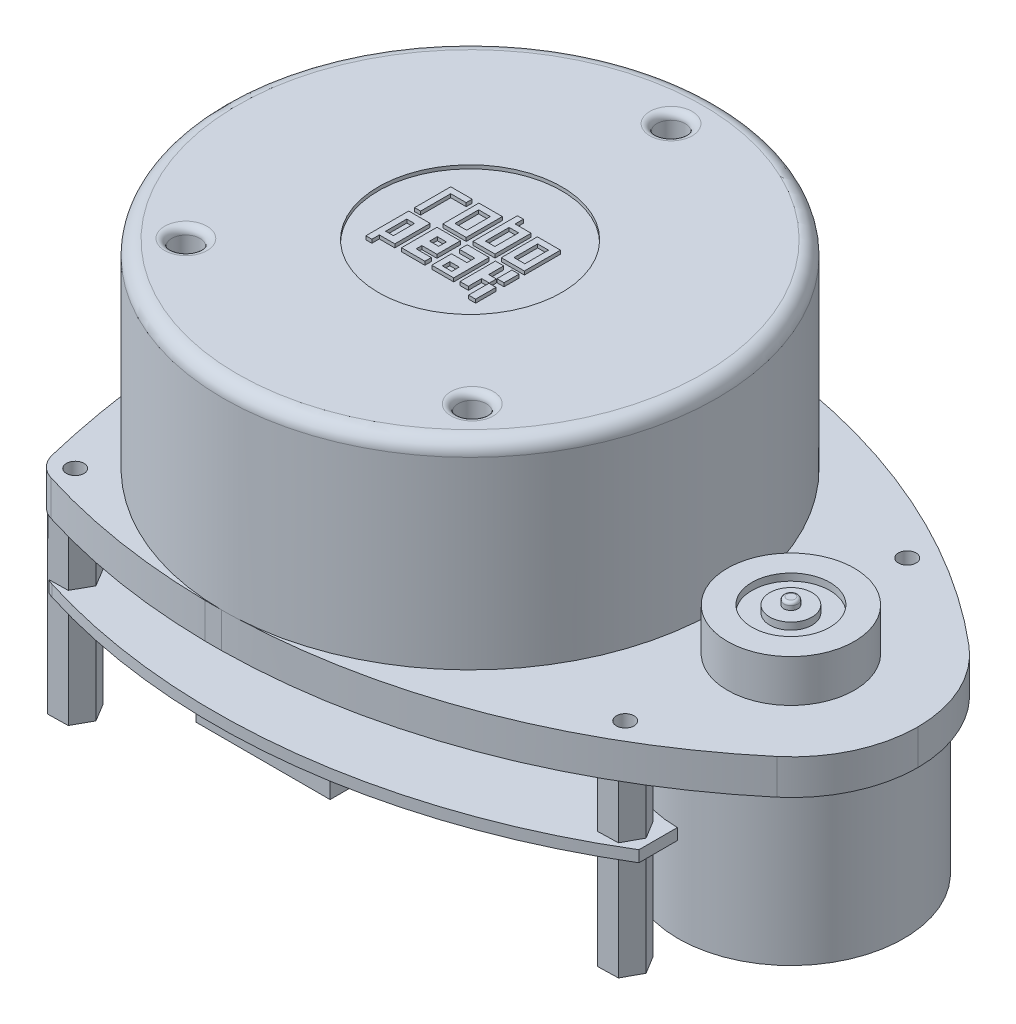
SolidWorks part; units mm, degrees
ref_plane "Спереди" through (0, 0, 0) normal (0, 0, 1) x (1, 0, 0)
ref_plane "Сверху" through (0, 0, 0) normal (0, 1, 0) x (1, 0, 0)
ref_plane "Справа" through (0, 0, 0) normal (1, 0, 0) x (0, 0, -1)
sketch "Эскиз1" plane through (0, 0, 0) normal (0, 1, 0) x (1, 0, 0)
  line L1 (-49.25, 35) -> (49.25, 35)
  line L2 (-49.25, 35) -> (-49.25, -35)
  line L3 (-49.25, -35) -> (49.25, -35)
  line L4 (49.25, 35) -> (49.25, -35)
  line L5 (-49.25, 35) -> (49.25, -35) construction
  line L6 (-49.25, -35) -> (49.25, 35) construction
  point P0 (0, 0)
  dimension "D1" = 98.5
  dimension "D2" = 70
extrude "Бобышка-Вытянуть1" add sketch "Эскиз1" along normal blind 5
sketch "Эскиз2" plane through (0, 5, 0) normal (0, 1, 0) x (1, 0, 0)
  line L0 (-49.25, 35) -> (-49.25, -35) construction
  circle A0 centre (-14.25, 0) radius 35
  point P2 (-49.25, 0)
  point P3 (-49.25, 0)
extrude "Бобышка-Вытянуть2" add sketch "Эскиз2" along normal blind 28.1
sketch "Эскиз3" plane through (0, 33.1, 0) normal (0, 1, 0) x (1, 0, 0)
  line L0 (-14.25, 0) -> (-14.25, 50000) construction
  line L1 (-14.25, -20) -> (-26.2883, -20) construction
  line L2 (-49.25, -35) -> (-14.25, -35) construction
  circle A0 centre (-14.25, 28.5) radius 2
  circle A1 centre (-34.5539, -20) radius 2
  circle A2 centre (6.0539, -20) radius 2
  arc A3 (-49.25, 0) -> (-14.25, -35) centre (-14.25, 0) ccw construction
  circle A4 centre (-14.25, 0) radius 35 construction
  dimension "D2" = 4
  dimension "D1" = 6.5
  dimension "D3" = 15
  dimension "D4" = 28.5
  dimension "D5" = 28.5
extrude "Вырез-Вытянуть1" cut sketch "Эскиз3" against normal blind 5
fillet "Скругление1" radius 2 1 edges at (-14.25, 33.1, 35)
fillet "Скругление2" radius 1 3 edges at (6.0539, 33.1, 22) (-34.5539, 33.1, 22) (-14.25, 33.1, -26.5)
sketch "Эскиз4" plane through (0, 33.1, 0) normal (0, 1, 0) x (1, 0, 0)
  line L0 (-22.1152, -6.9149) -> (-22.1152, -0.8316)
  line L1 (-22.1152, -0.8316) -> (-19.0735, -0.8316)
  line L2 (-19.0735, -0.8316) -> (-19.0735, -5.8538)
  line L3 (-19.0735, -5.8538) -> (-21.2663, -5.8538)
  line L4 (-21.2663, -5.8538) -> (-21.2663, -6.9149)
  line L5 (-21.2663, -6.9149) -> (-22.1152, -6.9149)
  line L6 (-22.1152, 0) -> (-22.1152, 5.1201)
  line L7 (-22.1152, 5.1201) -> (-19.0735, 5.1201)
  line L8 (-19.0735, 5.1201) -> (-19.0735, 4.2707)
  line L9 (-19.0735, 4.2707) -> (-21.2663, 4.2707)
  line L10 (-21.2663, 4.2707) -> (-21.2663, 0)
  line L11 (-21.2663, 0) -> (-22.1152, 0)
  line L12 (-21.2663, -1.9579) -> (-20.1699, -1.9579)
  line L13 (-20.1699, -1.9579) -> (-20.1699, -4.9509)
  line L14 (-20.1699, -4.9509) -> (-21.2663, -4.9509)
  line L15 (-21.2663, -4.9509) -> (-21.2663, -1.9579)
  line L16 (-13.8296, 0) -> (-13.8296, 6.293)
  line L17 (-18.1168, 0) -> (-14.8003, 0)
  line L18 (-18.1168, 0) -> (-18.1168, 5.1201)
  line L19 (-18.1168, 5.1201) -> (-14.8003, 5.1201)
  line L20 (-14.8003, 0) -> (-14.8003, 5.1201)
  line L21 (-9.8255, 5.1201) -> (-6.5494, 5.1201)
  line L22 (-9.8255, 5.1201) -> (-9.8255, 0)
  line L23 (-9.8255, 0) -> (-6.5494, 0)
  line L24 (-6.5494, 5.1201) -> (-6.5494, 0)
  line L25 (-8.9357, 4.2707) -> (-7.3988, 4.2707)
  line L26 (-8.9357, 4.2707) -> (-8.9357, 0.9137)
  line L27 (-8.9357, 0.9137) -> (-7.3988, 0.9137)
  line L28 (-7.3988, 4.2707) -> (-7.3988, 0.9137)
  line L29 (-17.3079, 4.2707) -> (-15.6497, 4.2707)
  line L30 (-17.3079, 4.2707) -> (-17.3079, 0.9137)
  line L31 (-17.3079, 0.9137) -> (-15.6497, 0.9137)
  line L32 (-15.6497, 4.2707) -> (-15.6497, 0.9137)
  line L33 (-12.9802, 4.2707) -> (-11.6455, 4.2707)
  line L34 (-12.9802, 4.2707) -> (-12.9802, 0.9137)
  line L35 (-12.9802, 0.9137) -> (-11.6455, 0.9137)
  line L36 (-11.6455, 4.2707) -> (-11.6455, 0.9137)
  line L37 (-12.9802, -4.142) -> (-11.6455, -4.142)
  line L38 (-12.9802, -4.142) -> (-12.9802, -5.1936)
  line L39 (-12.9802, -5.1936) -> (-11.6455, -5.1936)
  line L40 (-11.6455, -4.142) -> (-11.6455, -5.1936)
  line L41 (-16.9439, -1.9579) -> (-15.6497, -1.9579)
  line L42 (-16.9439, -1.9579) -> (-16.9439, -3.0499)
  line L43 (-16.9439, -3.0499) -> (-15.6497, -3.0499)
  line L44 (-15.6497, -1.9579) -> (-15.6497, -3.0499)
  line L46 (-7.5508, -0.7643) -> (-6.5494, -0.7643)
  line L47 (-7.5508, -0.7643) -> (-7.5508, -2.8858)
  line L48 (-7.5508, -2.8858) -> (-6.5494, -2.8858)
  line L49 (-6.5494, -0.7643) -> (-6.5494, -2.8858)
  line L50 (-6.5494, -6.9149) -> (-7.5508, -6.9149)
  line L51 (-6.5494, -6.9149) -> (-6.5494, -4.0216)
  line L52 (-6.5494, -4.0216) -> (-7.5508, -4.0216)
  line L53 (-13.8296, 6.293) -> (-12.9802, 6.293)
  line L54 (-12.9802, 6.293) -> (-12.9802, 5.1201)
  line L55 (-12.9802, 5.1201) -> (-10.7153, 5.1201)
  line L56 (-10.7153, 5.1201) -> (-10.7153, 0)
  line L57 (-10.7153, 0) -> (-13.8296, 0)
  line L58 (-9.8255, -0.8316) -> (-8.6437, -0.8316)
  line L59 (-8.6437, -0.8316) -> (-8.6437, -2.9608)
  line L60 (-8.6437, -2.9608) -> (-7.5508, -2.9608)
  line L61 (-9.8255, -0.8316) -> (-9.8255, -5.8538)
  line L62 (-9.8255, -5.8538) -> (-8.6437, -5.8538)
  line L63 (-8.6437, -5.8538) -> (-8.6437, -3.9573)
  line L64 (-8.6437, -3.9573) -> (-7.5508, -3.9573)
  line L65 (-7.5508, -2.9608) -> (-7.5508, -3.9573)
  line L66 (-13.8296, -0.8316) -> (-10.7153, -0.8316)
  line L67 (-10.7153, -0.8316) -> (-10.7153, -5.8538)
  line L68 (-10.7153, -5.8538) -> (-13.8296, -5.8538)
  line L69 (-13.8296, -5.8538) -> (-13.8296, -3.0499)
  line L70 (-13.8296, -3.0499) -> (-11.6455, -3.0499)
  line L71 (-11.6455, -3.0499) -> (-11.6455, -1.9408)
  line L72 (-11.6455, -1.9408) -> (-13.8296, -1.9408)
  line L73 (-13.8296, -1.9408) -> (-13.8296, -0.8316)
  line L74 (-18.1168, -0.8316) -> (-14.8003, -0.8316)
  line L75 (-14.8003, -0.8316) -> (-14.8003, -4.142)
  line L76 (-14.8003, -4.142) -> (-16.9439, -4.142)
  line L77 (-16.9439, -4.142) -> (-16.9439, -4.9509)
  line L78 (-16.9439, -4.9509) -> (-14.8003, -4.9509)
  line L79 (-14.8003, -4.9509) -> (-14.8003, -5.8538)
  line L80 (-14.8003, -5.8538) -> (-18.1168, -5.8538)
  line L81 (-18.1168, -5.8538) -> (-18.1168, -0.8316)
  line L82 (-7.5508, -6.9149) -> (-7.5508, -4.0216)
  circle A0 centre (-14.25, 0) radius 13
  dimension "D1" = 26
extrude "Вырез-Вытянуть3" cut sketch "Эскиз4" against normal blind 0.5 contours A0 L50 L82 L52 L51 L72 L73 L66 L67 L68 L69 L70 L71 L56 L57 L16 L53 L54 L55 L10 L11 L6 L7 L8 L9 L4 L5 L0 L1 L2 L3 L20 L17 L18 L19 L21 L24 L23 L22 L46 L49 L48 L47 | L32 L29 L30 L31 | L36 L33 L34 L35 | L28 L25 L26 L27 | L44 L41 L42 L43 | L15 L14 L13 L12 | L37 L40 L39 L38 region at (-20.7181, 33.1, 3.4544) region at (-8.1672, 33.1, -2.5922) region at (-16.4788, 33.1, -2.5922) region at (-12.3129, 33.1, -2.5922) region at (-16.2968, 33.1, 2.5039) region at (-14.2871, 33.1, -0.0991)
sketch "Эскиз5" plane through (0, 5, 0) normal (0, 1, 0) x (1, 0, 0)
  line L0 (-42.25, 30.7255) -> (-42.25, -39.5827) construction
  line L1 (27.75, 26.9972) -> (27.75, -49973.0028) construction
  line L2 (-49.25, 0) -> (49950.75, 0) construction
  circle A0 centre (-14.25, 0) radius 33 construction
  circle A1 centre (-42.25, 28) radius 1.25
  circle A2 centre (27.75, 20) radius 1.25
  circle A3 centre (27.75, -20) radius 1.25
  circle A4 centre (-42.25, -28) radius 1.25
  point P4 (-14.25, 33)
  dimension "D1" = 28
  dimension "D3" = 2.5
  dimension "D2" = 42
  dimension "D4" = 28
  dimension "D5" = 20
extrude "Вырез-Вытянуть4" cut sketch "Эскиз5" against normal blind 5
sketch "Эскиз6" plane through (0, 5, 0) normal (0, 1, 0) x (1, 0, 0)
  line L0 (49.25, 0) -> (50049.25, 0) construction
  line L1 (49.25, -35) -> (49.25, 35) construction
  circle A0 centre (31.25, 0) radius 9
  arc A1 (-14.25, -35) -> (-14.25, 35) centre (-14.25, 0) ccw construction
  point P4 (49.25, 0)
  dimension "D1" = 18
  dimension "D2" = 45.5
extrude "Бобышка-Вытянуть3" add sketch "Эскиз6" along normal blind 7
sketch "Эскиз7" plane through (0, 12, 0) normal (0, 1, 0) x (1, 0, 0)
  circle A0 centre (31.25, 0) radius 9
  circle A1 centre (31.25, 0) radius 0.9935
extrude "Вырез-Вытянуть5" cut sketch "Эскиз7" against normal blind 1
sketch "Эскиз8" plane through (0, 11, 0) normal (0, 1, 0) x (1, 0, 0)
  circle A0 centre (31.25, 0) radius 3.0011
  circle A1 centre (31.25, 0) radius 5.5217
extrude "Вырез-Вытянуть6" cut sketch "Эскиз8" against normal blind 1
fillet "Скругление3" radius 0.4 1 edges at (31.25, 12, 0.9935)
sketch "Эскиз9" plane through (0, 5, 0) normal (0, 1, 0) x (1, 0, 0)
  circle A0 centre (31.25, 0) radius 16
  dimension "D1" = 32
extrude "Бобышка-Вытянуть4" add sketch "Эскиз9" against normal blind 27
sketch "Эскиз10" plane through (0, 0, 0) normal (0, -1, 0) x (1, 0, 0)
  line L0 (-49.25, 0) -> (49950.75, 0) construction
  line L1 (-40.8546, 25.4729) -> (-39.3638, 27.9449)
  line L2 (-39.3638, 27.9449) -> (-40.7592, 30.472)
  line L3 (-40.7592, 30.472) -> (-43.6454, 30.5271)
  line L4 (-43.6454, 30.5271) -> (-45.1362, 28.0551)
  line L5 (-45.1362, 28.0551) -> (-43.7408, 25.528)
  line L6 (-43.7408, 25.528) -> (-40.8546, 25.4729)
  line L7 (29.2571, 22.4621) -> (26.3713, 22.5363)
  line L8 (26.3713, 22.5363) -> (24.8642, 20.0742)
  line L9 (24.8642, 20.0742) -> (26.2429, 17.5379)
  line L10 (26.2429, 17.5379) -> (29.1287, 17.4637)
  line L11 (29.1287, 17.4637) -> (30.6358, 19.9258)
  line L12 (30.6358, 19.9258) -> (29.2571, 22.4621)
  line L13 (30.6358, -19.9258) -> (29.2571, -22.4621)
  line L14 (29.1287, -17.4637) -> (30.6358, -19.9258)
  line L15 (26.2429, -17.5379) -> (29.1287, -17.4637)
  line L16 (24.8642, -20.0742) -> (26.2429, -17.5379)
  line L17 (26.3713, -22.5363) -> (24.8642, -20.0742)
  line L18 (29.2571, -22.4621) -> (26.3713, -22.5363)
  line L19 (-43.7408, -25.528) -> (-40.8546, -25.4729)
  line L20 (-45.1362, -28.0551) -> (-43.7408, -25.528)
  line L21 (-43.6454, -30.5271) -> (-45.1362, -28.0551)
  line L22 (-40.7592, -30.472) -> (-43.6454, -30.5271)
  line L23 (-39.3638, -27.9449) -> (-40.7592, -30.472)
  line L24 (-40.8546, -25.4729) -> (-39.3638, -27.9449)
  circle A0 centre (-42.25, 28) radius 2.5 construction
  circle A1 centre (27.75, 20) radius 2.5 construction
  circle A2 centre (27.75, -20) radius 2.5 construction
  circle A3 centre (-42.25, -28) radius 2.5 construction
  point P17 (27.75, 20)
  dimension "D1" = 5
  dimension "D2" = 5
extrude "Бобышка-Вытянуть5" add sketch "Эскиз10" along normal blind 24.6
sketch "Эскиз11" plane through (0, 5, 0) normal (0, 1, 0) x (1, 0, 0)
  circle A0 centre (-14.25, 0) radius 26
  dimension "D1" = 52
extrude "Бобышка-Вытянуть6" add sketch "Эскиз11" against normal blind 8
fillet "Скругление4" radius 1 1 edges at (-14.25, -3, 26)
sketch "Эскиз12" plane through (0, 5, 0) normal (0, 1, 0) x (1, 0, 0)
  line L1 (49.25, -35) -> (49.25, 35) construction
  line L2 (-49.25, 0) -> (-50049.25, 0) construction
  line L4 (-54.0511, 37.7308) -> (52.2004, 37.7308)
  line L5 (-54.0511, 37.7308) -> (-54.0511, -37.8351)
  line L6 (-54.0511, -37.8351) -> (52.2004, -37.8351)
  line L7 (52.2004, 37.7308) -> (52.2004, -37.8351)
  arc A0 (-49.25, 0) -> (-45.5286, 27.9743) centre (86.6751, -3.8473) cw
  circle A1 centre (-14.25, 0) radius 35 construction
  arc A3 (49.25, 0) -> (42.909, 13.5993) centre (31.4018, -0.0442) ccw
  arc A4 (-49.25, 0) -> (-14.25, -35) centre (-14.25, 0) ccw construction
  arc A5 (-42.835, 30.8555) -> (42.909, 13.5993) centre (-15.6796, -55.8665) cw
  arc A6 (-45.5286, 27.9743) -> (-42.835, 30.8555) centre (-41.6397, 27.0383) cw
  arc A7 (-45.5286, -27.9743) -> (-42.835, -30.8555) centre (-41.6397, -27.0383) ccw
  arc A8 (-42.835, -30.8555) -> (42.909, -13.5993) centre (-15.6796, 55.8665) ccw
  arc A9 (49.25, 0) -> (42.909, -13.5993) centre (31.4018, 0.0442) cw
  arc A10 (-49.25, 0) -> (-45.5286, -27.9743) centre (86.6751, 3.8473) ccw
  dimension "D1" = 4
extrude "Вырез-Вытянуть7" cut sketch "Эскиз12" against normal blind 8
fillet "Скругление5" radius 100 1 edges at (-49.25, 2.5, 0)
sketch "Эскиз13" plane through (0, 0, 0) normal (0, -1, 0) x (1, 0, 0)
  line L0 (31.5536, 21.8603) -> (31.5536, 16.4)
  line L1 (31.5536, -16.4) -> (31.5536, -21.8603)
  arc A0 (-49.0982, 0) -> (-45.3768, 27.9743) centre (86.8269, -3.8473) cw
  arc A1 (31.5536, 16.4) -> (31.5536, -16.4) centre (31.5536, 0) ccw
  arc A2 (-42.6831, 30.8555) -> (31.5536, 21.8603) centre (-15.5278, -55.8665) cw
  arc A3 (-45.3768, 27.9743) -> (-42.6831, 30.8555) centre (-41.4878, 27.0383) cw
  arc A4 (-45.3768, -27.9743) -> (-42.6831, -30.8555) centre (-41.4878, -27.0383) ccw
  arc A5 (-42.6831, -30.8555) -> (31.5536, -21.8603) centre (-15.5278, 55.8665) ccw
  arc A7 (-49.0982, 0) -> (-45.3768, -27.9743) centre (86.8269, 3.8473) ccw
  arc A8 (-48.5248, 10.6929) -> (-48.5248, -10.6929) centre (50.9018, 0) ccw construction
  point P16 (-49.0982, 0)
  point P21 (-49.0982, 0)
  dimension "D1" = 4
  dimension "D2" = 32.8
extrude "Бобышка-Вытянуть7" add sketch "Эскиз13" along normal blind 1.6 from offset 8
sketch "Эскиз14" plane through (0, -9.6, 0) normal (0, -1, 0) x (1, 0, 0)
  line L1 (-24.0982, 30) -> (-4.0982, 30)
  line L2 (-24.0982, 30) -> (-24.0982, 25)
  line L3 (-24.0982, 25) -> (-4.0982, 25)
  line L4 (-4.0982, 30) -> (-4.0982, 25)
  circle A0 centre (-14.25, 0) radius 35 construction
  point P4 (-14.0982, 30)
  dimension "D1" = 5
  dimension "D2" = 20
  dimension "D3" = 35
  dimension "D4" = 30
extrude "Бобышка-Вытянуть8" add sketch "Эскиз14" along normal blind 6
chamfer "Фаска1" distance 1 angle 45 1 edges at (-24.0982, -12.6, 30)
sketch "Sketch1" plane through (0, -24.6, 0) normal (0, -1, 0) x (1, 0, 0)
  line L0 (27.8142, 22.4992) -> (27.6858, 17.5008) construction
  line L1 (29.2571, 22.4621) -> (26.3713, 22.5363) construction
  line L2 (26.2429, 17.5379) -> (29.1287, 17.4637) construction
  line L3 (27.6858, -17.5008) -> (27.8142, -22.4992) construction
  line L4 (29.1287, -17.4637) -> (26.2429, -17.5379) construction
  line L5 (26.3713, -22.5363) -> (29.2571, -22.4621) construction
  line L6 (-42.2977, -25.5005) -> (-42.1051, -30.4977) construction
  line L7 (-40.8546, -25.4729) -> (-43.7408, -25.528) construction
  line L8 (-43.451, -30.5234) -> (-40.7592, -30.472) construction
  line L9 (-42.2023, 30.4995) -> (-42.2977, 25.5005) construction
  line L10 (-40.7592, 30.472) -> (-43.6454, 30.5271) construction
  line L11 (-43.7408, 25.528) -> (-40.8546, 25.4729) construction
  circle A0 centre (27.75, 20) radius 1.25
  circle A1 centre (27.75, -20) radius 1.25
  circle A2 centre (-42.2014, -27.9991) radius 1.25
  circle A3 centre (-42.25, 28) radius 1.25
  dimension "D1" = 2.5
extrude "Cut-Extrude1" cut sketch "Sketch1" against normal blind 15
